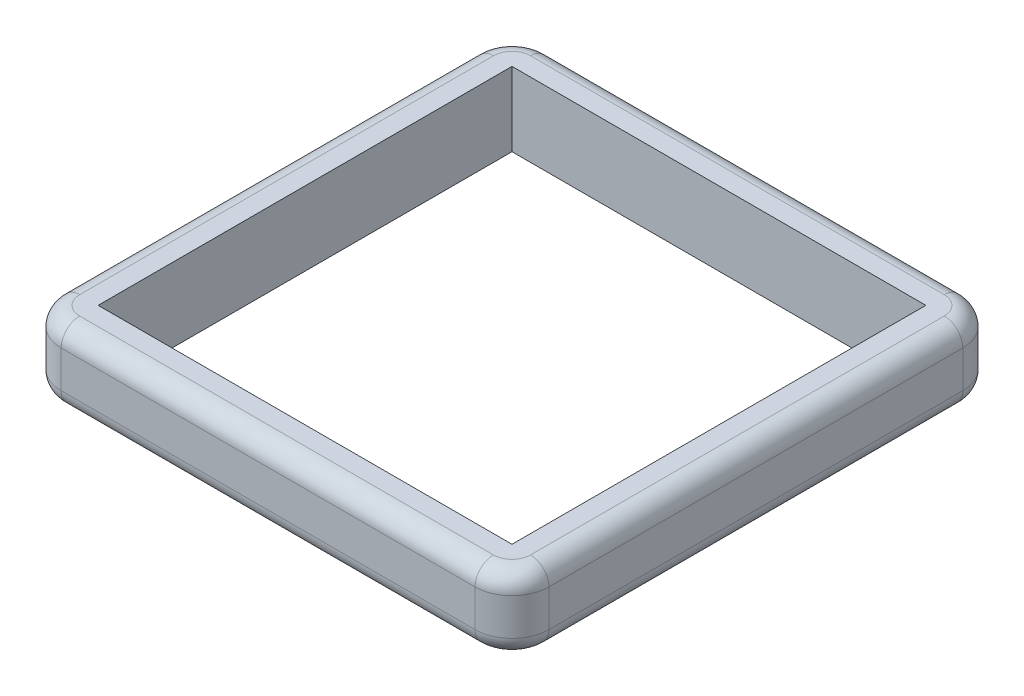
SolidWorks part; units mm, degrees
material "Polyurethane Foam Flexible"
ref_plane "Front Plane" through (0, 0, 0) normal (0, 0, 1) x (1, 0, 0)
ref_plane "Top Plane" through (0, 0, 0) normal (0, 1, 0) x (1, 0, 0)
ref_plane "Right Plane" through (0, 0, 0) normal (1, 0, 0) x (0, 0, -1)
sketch "Sketch1" plane through (0, 0, 0) normal (1, 0, 0) x (0, 0, -1)
  line L0 (-31.75, 0) -> (-31.75, -63.5)
  line L1 (31.75, 0) -> (31.75, -95.25)
  line L2 (0, -95.25) -> (31.75, -95.25)
  line L3 (31.75, 0) -> (31.75, 31.75)
  line L4 (0, 31.75) -> (31.75, 31.75)
  arc A0 (0, 31.75) -> (-31.75, 0) centre (0, 0) ccw
  arc A1 (-31.75, -63.5) -> (0, -95.25) centre (0, -63.5) ccw
  arc A2 (31.75, 0) -> (0, 31.75) centre (0, 0) ccw construction
  arc A3 (0, -31.75) -> (31.75, 0) centre (0, 0) ccw construction
  arc A4 (31.75, -63.5) -> (0, -31.75) centre (0, -63.5) ccw construction
  arc A5 (-31.75, 0) -> (0, -31.75) centre (0, 0) ccw construction
  arc A6 (0, -31.75) -> (-31.75, -63.5) centre (0, -63.5) ccw construction
  arc A7 (0, -95.25) -> (31.75, -63.5) centre (0, -63.5) ccw construction
  dimension "D1" = 63.5
  dimension "D2" = 63.5
extrude "Boss-Extrude1" add sketch "Sketch1" along normal blind 711.2 contours L0 A1 L2 L1 L3 L4 A0 region at (0, -31.75, -1.3979)
sketch "Sketch8" plane through (711.2, 0, 0) normal (1, 0, 0) x (0, 0, -1)
  line L8 (-31.75, 0) -> (-31.75, -63.5)
  line L9 (0, -95.25) -> (31.75, -95.25)
  line L10 (31.75, -95.25) -> (31.75, 31.75)
  line L11 (31.75, 31.75) -> (0, 31.75)
  line L12 (-31.75, 0) -> (-31.75, -63.5)
  line L13 (0, -95.25) -> (31.75, -95.25)
  line L14 (31.75, -95.25) -> (31.75, 31.75)
  line L15 (31.75, 31.75) -> (0, 31.75)
  arc A4 (-31.75, -63.5) -> (0, -95.25) centre (0, -63.5) ccw
  arc A5 (0, 31.75) -> (-31.75, 0) centre (0, 0) ccw
  arc A6 (-31.75, -63.5) -> (0, -95.25) centre (0, -63.5) ccw
  arc A7 (0, 31.75) -> (-31.75, 0) centre (0, 0) ccw
  dimension "D1" = 0
revolve "Revolve13" add sketch "Sketch8" angle 90 about L14
sketch "Sketch15" plane through (0, 0, -31.75) normal (-1, 0, 0) x (0, 0, 1)
  line L14 (63.5, -63.5) -> (63.5, 0)
  line L20 (31.75, 31.75) -> (0, 31.75)
  line L21 (0, 31.75) -> (0, -95.25)
  line L22 (0, -95.25) -> (31.75, -95.25)
  line L23 (63.5, -63.5) -> (63.5, 0)
  line L24 (31.75, 31.75) -> (0, 31.75)
  line L25 (0, 31.75) -> (0, -95.25)
  line L26 (0, -95.25) -> (31.75, -95.25)
  arc A8 (63.5, 0) -> (31.75, 31.75) centre (31.75, 0) ccw
  arc A9 (31.75, -95.25) -> (63.5, -63.5) centre (31.75, -63.5) ccw
  arc A10 (63.5, 0) -> (31.75, 31.75) centre (31.75, 0) ccw
  arc A11 (31.75, -95.25) -> (63.5, -63.5) centre (31.75, -63.5) ccw
  dimension "D1" = 0
revolve "Revolve12" add sketch "Sketch15" angle 90 about L25 region at (0, -31.75, -1.3979)
sketch "Sketch7" plane through (0, 0, -31.75) normal (0, 0, -1) x (-1, 0, 0)
  line L6 (-774.7, 0) -> (-774.7, -63.5)
  line L7 (-742.95, -95.25) -> (-711.2, -95.25)
  line L8 (-711.2, -95.25) -> (-711.2, 31.75)
  line L9 (-711.2, 31.75) -> (-742.95, 31.75)
  line L10 (-774.7, 0) -> (-774.7, -63.5)
  line L11 (-742.95, -95.25) -> (-711.2, -95.25)
  line L12 (-711.2, -95.25) -> (-711.2, 31.75)
  line L13 (-711.2, 31.75) -> (-742.95, 31.75)
  arc A4 (-742.95, 31.75) -> (-774.7, 0) centre (-742.95, 0) ccw
  arc A5 (-774.7, -63.5) -> (-742.95, -95.25) centre (-742.95, -63.5) ccw
  arc A6 (-742.95, 31.75) -> (-774.7, 0) centre (-742.95, 0) ccw
  arc A7 (-774.7, -63.5) -> (-742.95, -95.25) centre (-742.95, -63.5) ccw
  line M4 (-711.2, 31.75) -> (-711.2, -95.25)
  dimension "D1" = 0
extrude "Boss-Extrude3" add sketch "Sketch7" along normal blind 711.2 contours M4 | M4 region at (741.5521, -31.75, -31.75)
sketch "Sketch12" plane through (1454.15, 0, -742.95) normal (0, 0, -1) x (-1, 0, 0)
  line L13 (679.45, 0) -> (679.45, -63.5)
  line L20 (711.2, -95.25) -> (742.95, -95.25)
  line L21 (742.95, -95.25) -> (742.95, 31.75)
  line L22 (742.95, 31.75) -> (711.2, 31.75)
  line L23 (679.45, 0) -> (679.45, -63.5)
  line L24 (711.2, -95.25) -> (742.95, -95.25)
  line L25 (742.95, -95.25) -> (742.95, 31.75)
  line L26 (742.95, 31.75) -> (711.2, 31.75)
  arc A8 (679.45, -63.5) -> (711.2, -95.25) centre (711.2, -63.5) ccw
  arc A9 (711.2, 31.75) -> (679.45, 0) centre (711.2, 0) ccw
  arc A10 (679.45, -63.5) -> (711.2, -95.25) centre (711.2, -63.5) ccw
  arc A11 (711.2, 31.75) -> (679.45, 0) centre (711.2, 0) ccw
  dimension "D1" = 0
revolve "Revolve2" add sketch "Sketch12" angle 90 about L25 region at (741.5521, -31.75, -742.95)
sketch "Sketch9" plane through (0, 0, -31.75) normal (0, 0, -1) x (-1, 0, 0)
  line L0 (31.75, 31.75) -> (0, 31.75)
  line L1 (31.75, -95.25) -> (0, -95.25)
  line L2 (0, 31.75) -> (0, -95.25)
  line L3 (63.5, 0) -> (63.5, -63.5)
  line L4 (-711.2, 31.75) -> (0, 31.75) construction
  line L5 (0, -95.25) -> (0, 31.75) construction
  circle A0 centre (31.75, 0) radius 31.75
  circle A1 centre (31.75, -63.5) radius 31.75
  line M5 (0, -95.25) -> (0, 31.75)
  dimension "D1" = 63.5
  dimension "D2" = 0
  dimension "D3" = 0
extrude "Boss-Extrude4" add sketch "Sketch9" along normal blind 711.2 contours A0 L0 L2 | A0 | A1 A0 L2 | A1 L3 A0 | A1 | A1 L1 M5 region at (-7.0919, 24.6581, -31.75) region at (-31.75, 0, -31.75) region at (-56.4081, -31.75, -31.75) region at (-7.0919, -31.75, -31.75) region at (-31.75, -63.5, -31.75) region at (-7.0919, -88.1581, -31.75)
sketch "Sketch14" plane through (0, 0, -742.95) normal (0, 0, -1) x (-1, 0, 0)
  line L12 (0, 31.75) -> (0, -95.25)
  line L13 (0, -95.25) -> (31.75, -95.25)
  line L14 (63.5, -63.5) -> (63.5, 0)
  line L15 (31.75, 31.75) -> (0, 31.75)
  line L16 (0, 31.75) -> (0, -95.25)
  line L17 (0, -95.25) -> (31.75, -95.25)
  line L18 (63.5, -63.5) -> (63.5, 0)
  line L19 (31.75, 31.75) -> (0, 31.75)
  arc A4 (31.75, -95.25) -> (63.5, -63.5) centre (31.75, -63.5) ccw
  arc A5 (63.5, 0) -> (31.75, 31.75) centre (31.75, 0) ccw
  arc A6 (31.75, -95.25) -> (63.5, -63.5) centre (31.75, -63.5) ccw
  arc A7 (63.5, 0) -> (31.75, 31.75) centre (31.75, 0) ccw
  dimension "D1" = 0
revolve "Revolve10" add sketch "Sketch14" angle 90 about L16 region at (-30.3521, -31.75, -742.95)
sketch "Sketch10" plane through (0, 0, 0) normal (1, 0, 0) x (0, 0, -1)
  line L4 (774.7, 31.75) -> (742.95, 31.75)
  line L7 (742.95, 31.75) -> (742.95, -95.25)
  line L8 (742.95, -95.25) -> (774.7, -95.25)
  line L9 (806.45, -63.5) -> (806.45, 0)
  line L10 (774.7, 31.75) -> (742.95, 31.75)
  line L12 (742.95, -95.25) -> (774.7, -95.25)
  line L13 (806.45, -63.5) -> (806.45, 0)
  line L15 (742.95, 31.75) -> (742.95, -95.25)
  arc A4 (774.7, -95.25) -> (806.45, -63.5) centre (774.7, -63.5) ccw
  arc A5 (806.45, 0) -> (774.7, 31.75) centre (774.7, 0) ccw
  arc A6 (774.7, -95.25) -> (806.45, -63.5) centre (774.7, -63.5) ccw
  arc A7 (806.45, 0) -> (774.7, 31.75) centre (774.7, 0) ccw
  line M7 (742.95, -95.25) -> (742.95, 31.75)
  dimension "D1" = 0
extrude "Boss-Extrude5" add sketch "Sketch10" along normal blind 711.2 separate body contours M7 | M7 region at (0, -31.75, -773.3021)
combine bodies "Combine1" operation type add bodies to combine 105 115 108
equation "\"foamlength\"=28"
equation "\"D1@Boss-Extrude1\"=\"foamlength\""
equation "\"D1@Boss-Extrude3\"=\"foamlength\""
equation "\"D1@Boss-Extrude4\"=\"foamlength\""
equation "\"D1@Boss-Extrude5\"=\"foamlength\""
